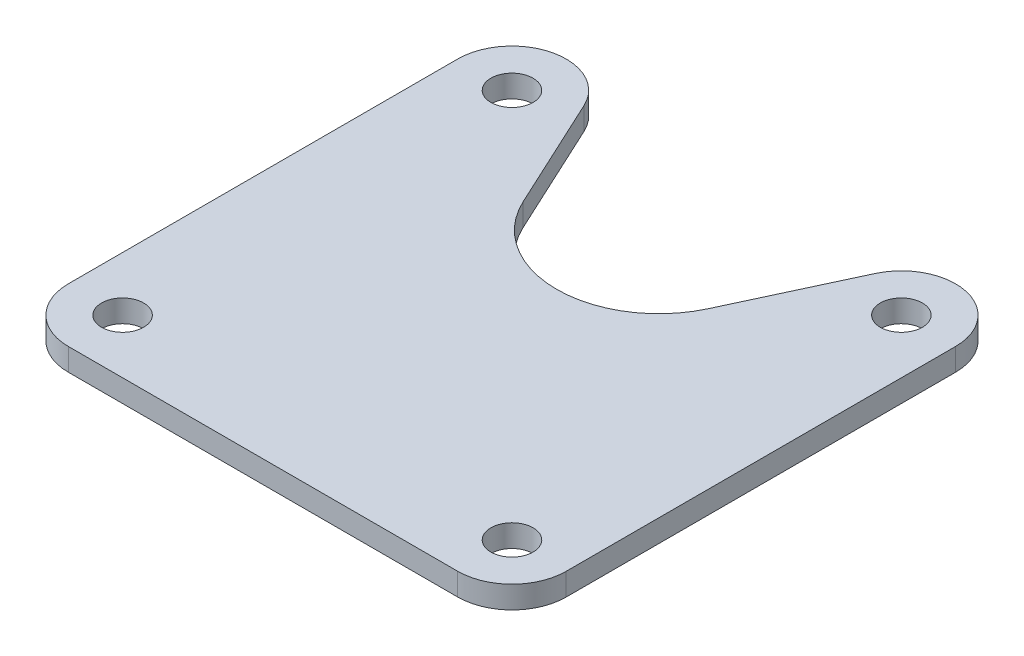
SolidWorks part; units mm, degrees
ref_plane "Front Plane" through (0, 0, 0) normal (0, 0, 1) x (1, 0, 0)
ref_plane "Top Plane" through (0, 0, 0) normal (0, 1, 0) x (1, 0, 0)
ref_plane "Right Plane" through (0, 0, 0) normal (1, 0, 0) x (0, 0, -1)
sketch "Sketch1" plane through (0, 0, 0) normal (0, 1, 0) x (1, 0, 0)
  line L0 (0, 19.5) -> (0, -19.5) construction
  line L1 (-19.5, 19.5) -> (19.5, 19.5)
  line L2 (-19.5, 19.5) -> (-19.5, -19.5)
  line L3 (-19.5, -19.5) -> (19.5, -19.5)
  line L4 (19.5, 19.5) -> (19.5, -19.5)
  line L5 (-19.5, 19.5) -> (19.5, -19.5) construction
  line L6 (-19.5, -19.5) -> (19.5, 19.5) construction
  line L7 (-19.5, 35.2) -> (-19.5, -19.5) construction
  circle A0 centre (-15.25, 15.25) radius 1.65
  circle A1 centre (15.25, 15.25) radius 1.65
  circle A2 centre (-15.25, -15.25) radius 1.65
  circle A3 centre (15.25, -15.25) radius 1.65
  circle A4 centre (15.25, 15.25) radius 1.65 construction
  circle A5 centre (15.25, -15.25) radius 1.65 construction
  circle A6 centre (-15.25, -15.25) radius 1.65 construction
  circle A7 centre (-15.25, 15.25) radius 1.65 construction
  point P0 (0, 0)
extrude "Shape" add sketch "Sketch1" along normal blind 1.75
sketch "Sketch2" plane through (0, 1.75, 0) normal (0, 1, 0) x (1, 0, 0)
  line L0 (0, 19.5) -> (0, -19.5) construction
  line L2 (-15.25, 16.9) -> (-15.25, -16.9) construction
  line L3 (-15.25, 0) -> (-19.5, 0) construction
  line L4 (-19.5, 19.5) -> (-19.5, -19.5) construction
  line L5 (19.5, 19.5) -> (-19.5, 19.5) construction
  line L6 (-19.5, -19.5) -> (19.5, -19.5) construction
  line L7 (-15.25, 0) -> (-11, 0) construction
  line L8 (-7.2551, 8.1291) -> (-12.5383, 19.5)
  line L9 (7.2551, 8.1291) -> (12.5383, 19.5)
  line L10 (-12.5383, 19.5) -> (12.5383, 19.5)
  line L14 (19.5, -19.5) -> (19.5, 19.5)
  line L15 (19.5, 19.5) -> (-19.5, 19.5)
  line L16 (-19.5, 19.5) -> (-19.5, -19.5)
  line L17 (-19.5, -19.5) -> (19.5, -19.5)
  line L18 (19.5, -19.5) -> (19.5, 19.5)
  line L19 (19.5, 19.5) -> (-19.5, 19.5)
  line L20 (-19.5, 19.5) -> (-19.5, -19.5)
  line L21 (-19.5, -19.5) -> (19.5, -19.5)
  circle A0 centre (0, 11.5) radius 8
  circle A1 centre (-15.25, 15.25) radius 1.65 construction
  circle A2 centre (-15.25, -15.25) radius 1.65 construction
  circle A3 centre (-15.25, 15.25) radius 4.25
  circle A4 centre (15.25, 15.25) radius 4.25
  circle A5 centre (-15.25, -15.25) radius 4.25
  circle A6 centre (15.25, -15.25) radius 4.25
  line M3 (19.5, -19.5) -> (19.5, 19.5)
  line M4 (19.5, 19.5) -> (-19.5, 19.5)
  line M5 (-19.5, 19.5) -> (-19.5, -19.5)
  line M6 (-19.5, -19.5) -> (19.5, -19.5)
  dimension "D1" = 16
  dimension "D2" = 0
extrude "Camera cut" cut sketch "Sketch2" against normal up to next contours A0 L10 L8 | A0 | A0 L9 M4 | A3 L8 M4 | A4 L9 M4 | A3 L19 M5 | A4 L18 M4 | A6 M6 M3 | A5 M5 M6 region at (0, 1.75, -11.5) region at (-8.2479, 1.75, -16.7625) region at (-12.8704, 1.75, -18.9795) region at (8.2479, 1.75, -16.7625) region at (-18.5507, 1.75, -18.5507) region at (12.8704, 1.75, -18.9795) region at (18.5507, 1.75, -18.5507) region at (-18.5507, 1.75, 18.5507) region at (18.5507, 1.75, 18.5507)
